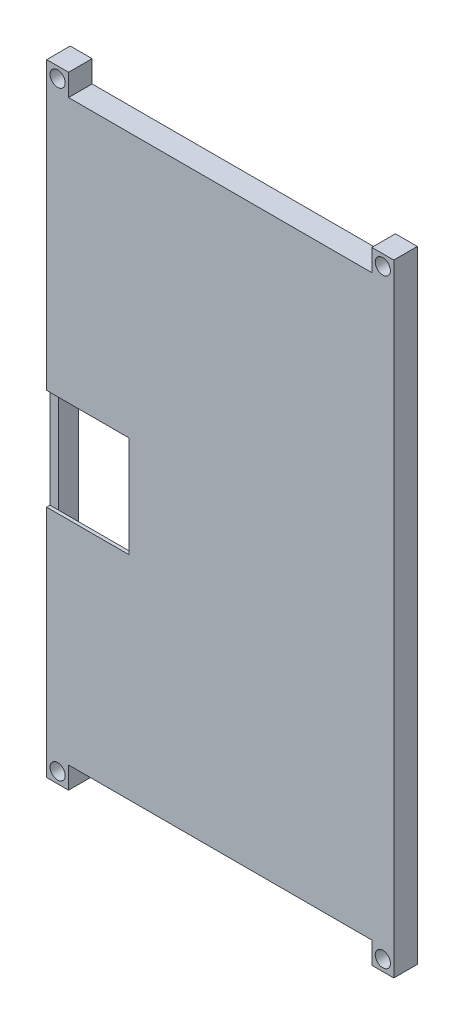
SolidWorks part; units mm, degrees
ref_plane "Ön Düzlem" through (0, 0, 0) normal (1, 0, 0) x (0, 1, 0)
ref_plane "Üst Düzlem" through (0, 0, 0) normal (0, 0, 1) x (0, 1, 0)
ref_plane "Sağ Düzlem" through (0, 0, 0) normal (0, 1, 0) x (-1, 0, 0)
sketch "Çizim1" plane through (0, 0, 0) normal (0, 0, 1) x (0, 1, 0)
  line L0 (-35.9386, 27.5204) -> (128.0614, 27.5204)
  line L1 (-35.9386, 27.5204) -> (-35.9386, -70.4796)
  line L2 (-35.9386, -70.4796) -> (128.0614, -70.4796)
  line L3 (128.0614, -70.4796) -> (128.0614, 27.5204)
  line L4 (128.0614, 27.5204) -> (133.0614, 27.5204) construction
  line L5 (133.0614, 27.5204) -> (133.0614, 30.0204) construction
  line L6 (133.0614, 30.0204) -> (150.9817, 30.0204) construction
  line L7 (133.0614, 27.5204) -> (133.0614, 18.0798) construction
  line L8 (128.0614, -70.4796) -> (128.0614, -72.9796) construction
  line L9 (128.0614, -72.9796) -> (133.0614, -72.9796) construction
  line L10 (-35.9386, 0) -> (-38.4386, 0) construction
  line L11 (-38.4386, 0) -> (-38.4386, 30.0204) construction
  line L12 (-38.4386, 30.0204) -> (-38.4386, -72.9796)
  line L13 (-38.4386, -72.9796) -> (133.0614, -72.9796)
  line L14 (133.0614, -72.9796) -> (133.0614, 30.0204)
  line L15 (133.0614, 30.0204) -> (-38.4386, 30.0204)
extrude "Yükseklik-Ekstrüzyon1" add sketch "Çizim1" along normal blind 6
sketch "Çizim2" plane through (0, 0, 6) normal (0, 0, 1) x (1, 0, 0)
  line L0 (-30.0204, 54.5614) -> (-30.0204, 133.0614)
  line L1 (-30.0204, -38.4386) -> (72.9796, -38.4386)
  line L2 (-30.0204, -38.4386) -> (-30.0204, 24.5614)
  line L3 (-30.0204, 133.0614) -> (72.9796, 133.0614)
  line L4 (72.9796, -38.4386) -> (72.9796, 133.0614)
  line L5 (-27.5204, 128.0614) -> (-27.5204, -35.9386) construction
  line L6 (-27.5204, 24.5614) -> (-5.5204, 24.5614)
  line L7 (-5.5204, 24.5614) -> (-5.5204, 54.5614)
  line L8 (-5.5204, 54.5614) -> (-27.5204, 54.5614)
  line L10 (-27.5204, 24.5614) -> (-30.0204, 24.5614)
  line L11 (-27.5204, 54.5614) -> (-30.0204, 54.5614)
extrude "Yükseklik-Ekstrüzyon2" add sketch "Çizim2" along normal blind 1
sketch "Çizim3" plane through (0, 0, 0) normal (0, 0, 1) x (0, 1, 0)
  line L0 (-38.4386, 30.0204) -> (-38.4386, 23.5204)
  line L1 (-38.4386, 30.0204) -> (-38.4386, -72.9796) construction
  line L2 (-38.4386, 30.0204) -> (-44.9386, 30.0204)
  line L3 (-44.9386, 30.0204) -> (-44.9386, 23.5204)
  line L4 (-44.9386, 23.5204) -> (-38.4386, 23.5204)
  line L5 (-44.9386, 23.5204) -> (-38.4386, 30.0204) construction
  line L6 (-38.4386, -72.9796) -> (-44.9386, -72.9796)
  line L7 (-44.9386, -72.9796) -> (-44.9386, -66.4796)
  line L8 (-44.9386, -66.4796) -> (-38.4386, -66.4796)
  line L9 (-38.4386, -66.4796) -> (-38.4386, -72.9796)
  line L10 (-44.9386, -72.9796) -> (-38.4386, -66.4796) construction
  line L11 (133.0614, 30.0204) -> (139.5614, 30.0204)
  line L12 (139.5614, 30.0204) -> (139.5614, 23.5204)
  line L13 (139.5614, 23.5204) -> (133.0614, 23.5204)
  line L14 (133.0614, -72.9796) -> (133.0614, 30.0204) construction
  line L15 (133.0614, 23.5204) -> (133.0614, 30.0204)
  line L16 (133.0614, 23.5204) -> (139.5614, 30.0204) construction
  line L17 (133.0614, -72.9796) -> (133.0614, -66.4796)
  line L18 (133.0614, -66.4796) -> (139.5614, -66.4796)
  line L19 (139.5614, -66.4796) -> (139.5614, -72.9796)
  line L20 (139.5614, -72.9796) -> (133.0614, -72.9796)
  circle A0 centre (-41.6886, 26.7704) radius 2.25
  circle A1 centre (-41.6886, -69.7296) radius 2.25
  circle A2 centre (136.3114, 26.7704) radius 2.25
  circle A3 centre (136.3114, -69.7296) radius 2.25
extrude "Yükseklik-Ekstrüzyon3" add sketch "Çizim3" along normal up to surface (7 mm away) up to face at (1.8546, 43.4364, 7)
